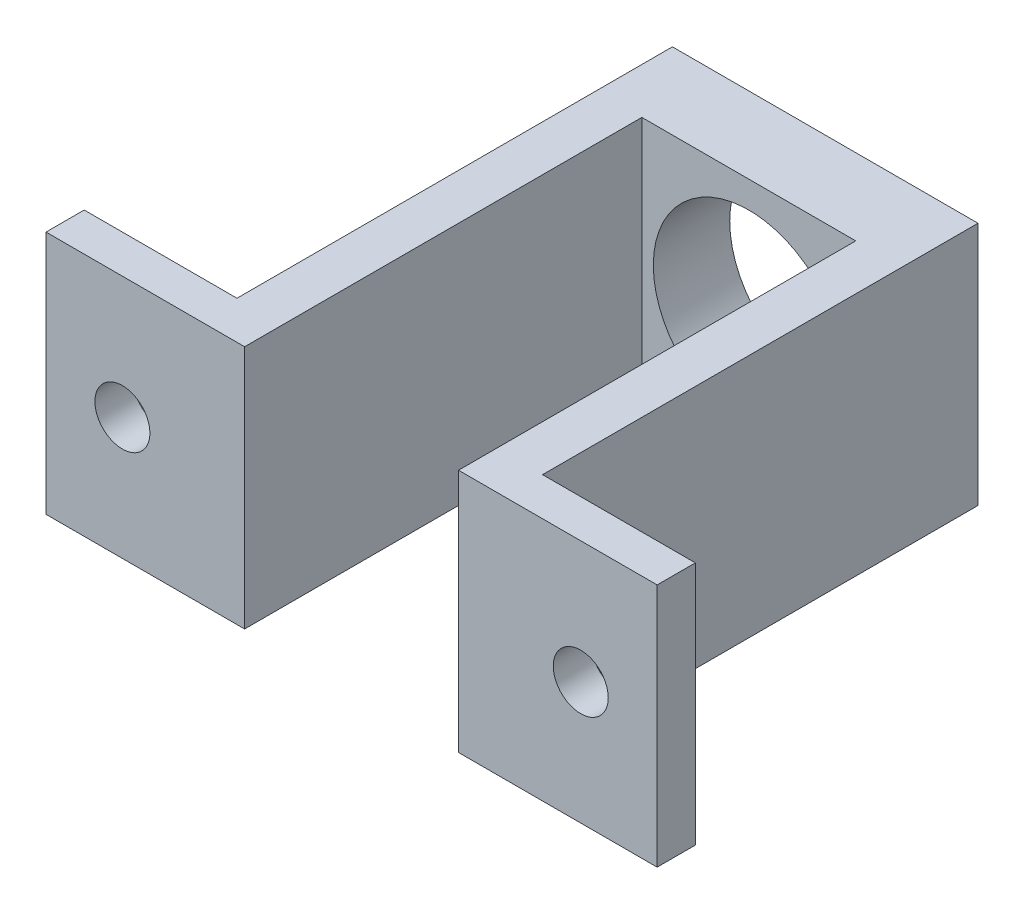
SolidWorks part; units mm, degrees
ref_plane "Front Plane" through (0, 0, 0) normal (0, 0, 1) x (1, 0, 0)
ref_plane "Top Plane" through (0, 0, 0) normal (0, 1, 0) x (1, 0, 0)
ref_plane "Right Plane" through (0, 0, 0) normal (1, 0, 0) x (0, 0, -1)
sketch "Sketch1" plane through (0, 0, 0) normal (0, 0, 1) x (1, 0, 0)
  line L1 (10, -8) -> (-10, -8)
  line L2 (10, -8) -> (10, 8)
  line L3 (10, 8) -> (-10, 8)
  line L4 (-10, -8) -> (-10, 8)
  line L5 (10, -8) -> (-10, 8) construction
  line L6 (10, 8) -> (-10, -8) construction
  circle A0 centre (0, 0) radius 6.25
  dimension "D1" = 12.5
  dimension "D2" = 20
  dimension "D3" = 16
extrude "Boss-Extrude1" add sketch "Sketch1" along normal blind 5
sketch "Sketch2" plane through (0, 0, 5) normal (0, 0, 1) x (1, 0, 0)
  line L0 (-10, -8) -> (10, -8) construction
  line L1 (-10, 8) -> (-7, 8)
  line L2 (-10, 8) -> (-10, -8)
  line L3 (-10, -8) -> (-7, -8)
  line L4 (-7, 8) -> (-7, -8)
  line L5 (0, -8) -> (0, 8) construction
  line L6 (10, 8) -> (-10, 8) construction
  line L7 (7, 8) -> (7, -8)
  line L8 (10, -8) -> (7, -8)
  line L9 (10, 8) -> (10, -8)
  line L10 (10, 8) -> (7, 8)
  dimension "D1" = 7
extrude "Boss-Extrude2" add sketch "Sketch2" along normal blind 26
sketch "Sketch3" plane through (0, 0, 31) normal (0, 0, 1) x (1, 0, 0)
  line L0 (-7, 8) -> (-10, 8) construction
  line L1 (-7, -8) -> (-20, -8)
  line L2 (-7, -8) -> (-7, 8)
  line L3 (-7, 8) -> (-20, 8)
  line L4 (-20, -8) -> (-20, 8)
  line L5 (-10, 8) -> (-10, -8) construction
  line L6 (0, 8) -> (0, -8) construction
  line L7 (7, 8) -> (-7, 8) construction
  line L8 (-7, -8) -> (7, -8) construction
  line L9 (20, -8) -> (20, 8)
  line L10 (7, 8) -> (20, 8)
  line L11 (7, -8) -> (7, 8)
  line L12 (7, -8) -> (20, -8)
  dimension "D1" = 0
  dimension "D2" = 10
extrude "Boss-Extrude3" add sketch "Sketch3" against normal blind 2.5
sketch "Sketch4" plane through (0, 0, 28.5) normal (0, 0, -1) x (-1, 0, 0)
  line L0 (-20, -5) -> (-10, -5) construction
  line L3 (0, -8) -> (0, 8) construction
  line L4 (10, -8) -> (-10, -8) construction
  line L5 (-10, 8) -> (10, 8) construction
  line L6 (-20, -5) -> (-10, -5) construction
  line L7 (-20, -3.25) -> (-10, -3.25)
  line L8 (-20, -6.75) -> (-10, -6.75)
  line L9 (20, 0) -> (10, 0) construction
  line L10 (20, -5) -> (10, -5) construction
  line L11 (22.5, 5) -> (12.5, 5) construction
  line L12 (22.5, 6.75) -> (12.5, 6.75)
  line L13 (-10, -8) -> (-10, 8) construction
  line L14 (-20, -8) -> (-20, 8) construction
  line L15 (-10, -8) -> (-20, -8) construction
  line L16 (-20, 0) -> (-10, 0) construction
  line L17 (-10, -8) -> (-10, 8) construction
  line L18 (-21.25, 0) -> (-11.25, 0) construction
  line L19 (-21.25, 1.75) -> (-11.25, 1.75)
  line L20 (-21.25, -1.75) -> (-11.25, -1.75)
  line L21 (-22.5, 5) -> (-12.5, 5) construction
  line L22 (-22.5, 6.75) -> (-12.5, 6.75)
  line L23 (-22.5, 3.25) -> (-12.5, 3.25)
  line L24 (22.5, 3.25) -> (12.5, 3.25)
  line L25 (21.25, 0) -> (11.25, 0) construction
  line L26 (21.25, 1.75) -> (11.25, 1.75)
  line L27 (21.25, -1.75) -> (11.25, -1.75)
  line L28 (20, -5) -> (10, -5) construction
  line L29 (20, -3.25) -> (10, -3.25)
  line L30 (20, -6.75) -> (10, -6.75)
  arc A0 (-20, -3.25) -> (-20, -6.75) centre (-20, -5) ccw
  arc A1 (-10, -6.75) -> (-10, -3.25) centre (-10, -5) ccw
  arc A2 (22.5, 6.75) -> (22.5, 3.25) centre (22.5, 5) cw
  arc A3 (12.5, 3.25) -> (12.5, 6.75) centre (12.5, 5) cw
  arc A4 (-21.25, 1.75) -> (-21.25, -1.75) centre (-21.25, 0) ccw
  arc A5 (-11.25, -1.75) -> (-11.25, 1.75) centre (-11.25, 0) ccw
  arc A6 (-22.5, 6.75) -> (-22.5, 3.25) centre (-22.5, 5) ccw
  arc A7 (-12.5, 3.25) -> (-12.5, 6.75) centre (-12.5, 5) ccw
  arc A8 (21.25, 1.75) -> (21.25, -1.75) centre (21.25, 0) cw
  arc A9 (11.25, -1.75) -> (11.25, 1.75) centre (11.25, 0) cw
  arc A10 (20, -3.25) -> (20, -6.75) centre (20, -5) cw
  arc A11 (10, -6.75) -> (10, -3.25) centre (10, -5) cw
  point P14 (-15, -5)
  point P25 (17.5, 5)
  point P28 (-15, -8)
  point P39 (-16.25, 0)
  point P46 (-17.5, 5)
  point P53 (16.25, 0)
  point P60 (15, -5)
  dimension "D1" = 1.75
  dimension "D8" = 2.5
  dimension "D2" = 10
  dimension "D3" = 0
  dimension "D4" = 0
  dimension "D5" = 3
  dimension "D7" = 10
  dimension "D6" = 3
extrude "Cut-Extrude1" [suppressed] cut sketch "Sketch4" against normal through all
sketch "Sketch5" plane through (0, 0, 31) normal (0, 0, 1) x (1, 0, 0)
  line L0 (-20, 0) -> (20, 0) construction
  line L1 (-20, 8) -> (-20, -8) construction
  line L2 (20, -8) -> (20, 8) construction
  line L3 (0, 0) -> (0, 8) construction
  line L4 (7, 8) -> (-7, 8) construction
  circle A0 centre (-15, 0) radius 1.8
  circle A1 centre (15, 0) radius 1.8
  dimension "D1" = 3.6
  dimension "D2" = 15
extrude "Cut-Extrude2" cut sketch "Sketch5" against normal through all
